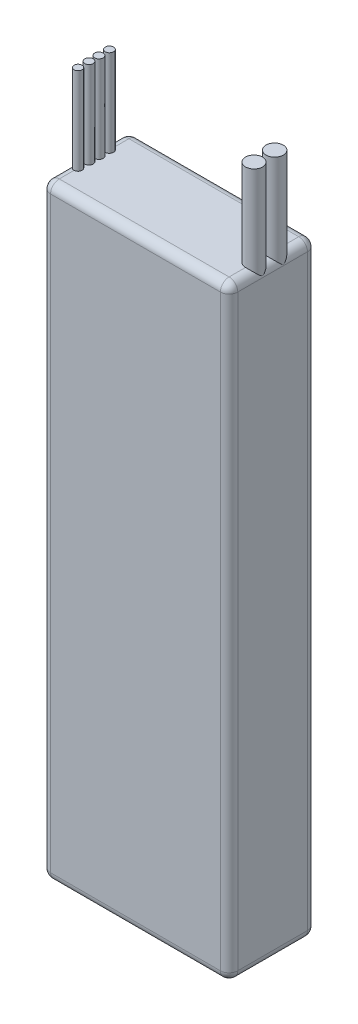
SolidWorks part; units mm, degrees
ref_plane "Front Plane" through (0, 0, 0) normal (0, 0, 1) x (1, 0, 0)
ref_plane "Top Plane" through (0, 0, 0) normal (0, 1, 0) x (1, 0, 0)
ref_plane "Right Plane" through (0, 0, 0) normal (1, 0, 0) x (0, 0, -1)
sketch "Sketch1" plane through (0, 0, 0) normal (0, 1, 0) x (1, 0, 0)
  line L1 (0, 20) -> (43, 20)
  line L2 (0, 20) -> (0, 0)
  line L3 (0, 0) -> (43, 0)
  line L4 (43, 20) -> (43, 0)
  dimension "D1" = 20
  dimension "D2" = 43
extrude "Boss-Extrude1" add sketch "Sketch1" along normal blind 139
fillet "Fillet1" radius 2 12 edges at (21.5, 0, -20) (0, 69.5, -20) (0, 0, -10) (21.5, 139, -20) (0, 139, -10) (43, 139, -10) (43, 69.5, -20) (43, 0, -10) (0, 69.5, 0) (21.5, 139, 0) (43, 69.5, 0) (21.5, 0, 0)
sketch "Sketch2" plane through (0, 139, 0) normal (0, 1, 0) x (1, 0, 0)
  line L2 (41, 2) -> (41, 18) construction
  line L3 (2, 18) -> (2, 2) construction
  circle A0 centre (41, 7.7313) radius 1.96
  circle A1 centre (41, 12.4677) radius 1.9883
  circle A2 centre (2, 6.3279) radius 0.9186
  circle A3 centre (2, 11.1081) radius 0.9712
  circle A4 centre (2, 13.5202) radius 0.9539
  circle A5 centre (2, 8.8277) radius 0.951
  point P2 (41, 7.7313)
  point P10 (41, 12.4677)
  point P17 (2, 6.3279)
  point P18 (2, 8.8277)
  point P20 (2, 11.1081)
  point P21 (2, 13.5202)
extrude "Boss-Extrude2" add sketch "Sketch2" along normal blind 20 and the other way up to next
